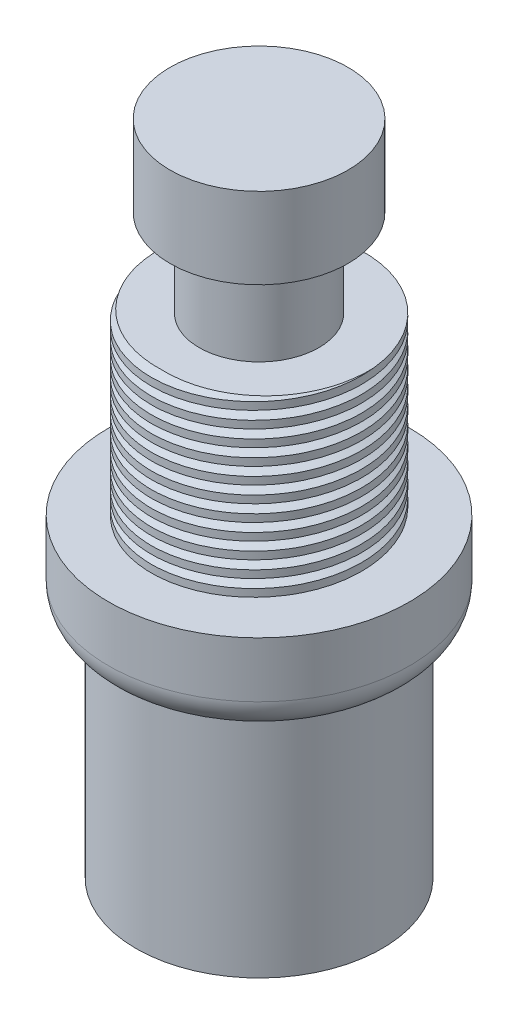
SolidWorks part; units mm, degrees
ref_plane "Front Plane" through (0, 0, 0) normal (0, 0, 1) x (1, 0, 0)
ref_plane "Top Plane" through (0, 0, 0) normal (0, 1, 0) x (1, 0, 0)
ref_plane "Right Plane" through (0, 0, 0) normal (1, 0, 0) x (0, 0, -1)
sketch "Sketch1" plane through (0, 0, 0) normal (0, 1, 0) x (1, 0, 0)
  circle A0 centre (0, 0) radius 3.8
  dimension "D1" = 7.6
extrude "Boss-Extrude1" add sketch "Sketch1" along normal blind 7
sketch "Sketch2" plane through (0, 7, 0) normal (0, 1, 0) x (1, 0, 0)
  circle A0 centre (0, 0) radius 4.65
  dimension "D1" = 9.3
extrude "Boss-Extrude2" add sketch "Sketch2" along normal blind 2.7
sketch "Sketch3" plane through (0, 9.7, 0) normal (0, 1, 0) x (1, 0, 0)
  circle A0 centre (0, 0) radius 3.25
  dimension "D1" = 6.5
extrude "Boss-Extrude3" add sketch "Sketch3" along normal blind 5.4
sketch "Sketch5" plane through (0, 15.1, 0) normal (0, 1, 0) x (1, 0, 0)
  circle A0 centre (0, 0) radius 3.25 construction
  circle A1 centre (0, 0) radius 3.25
curve "Helix/Spiral1" pitch 0.5 height 5.4 radius 3.25 centre (0, 15.1, 0) axis (0, -1, 0) start towards (0, 0, 1)
sketch "Sketch6" plane through (0, 0, 0) normal (1, 0, 0) x (0, 0, -1)
  line L1 (-3.0191, 15.1) -> (-3.3655, 15.3)
  line L2 (-3.3655, 15.3) -> (-3.3655, 14.9)
  line L3 (-3.3655, 14.9) -> (-3.0191, 15.1)
  circle A0 centre (-3.25, 15.1) radius 0.1155 construction
  dimension "D1" = 0.4
sweep "Cut-Sweep1" cut profiles "Sketch6" path "Helix/Spiral1" align with end faces yes
sketch "Sketch7" plane through (0, 15.1, 0) normal (0, 1, 0) x (1, 0, 0)
  circle A0 centre (0, 0) radius 1.85
  dimension "D1" = 3.7
extrude "Boss-Extrude4" add sketch "Sketch7" along normal blind 2.7
sketch "Sketch8" plane through (0, 17.8, 0) normal (0, 1, 0) x (1, 0, 0)
  circle A0 centre (0, 0) radius 2.75
  dimension "D1" = 5.5
extrude "Boss-Extrude5" add sketch "Sketch8" along normal blind 2.5
fillet "Fillet1" radius 1 1 edges at (0, 7, 4.65)
